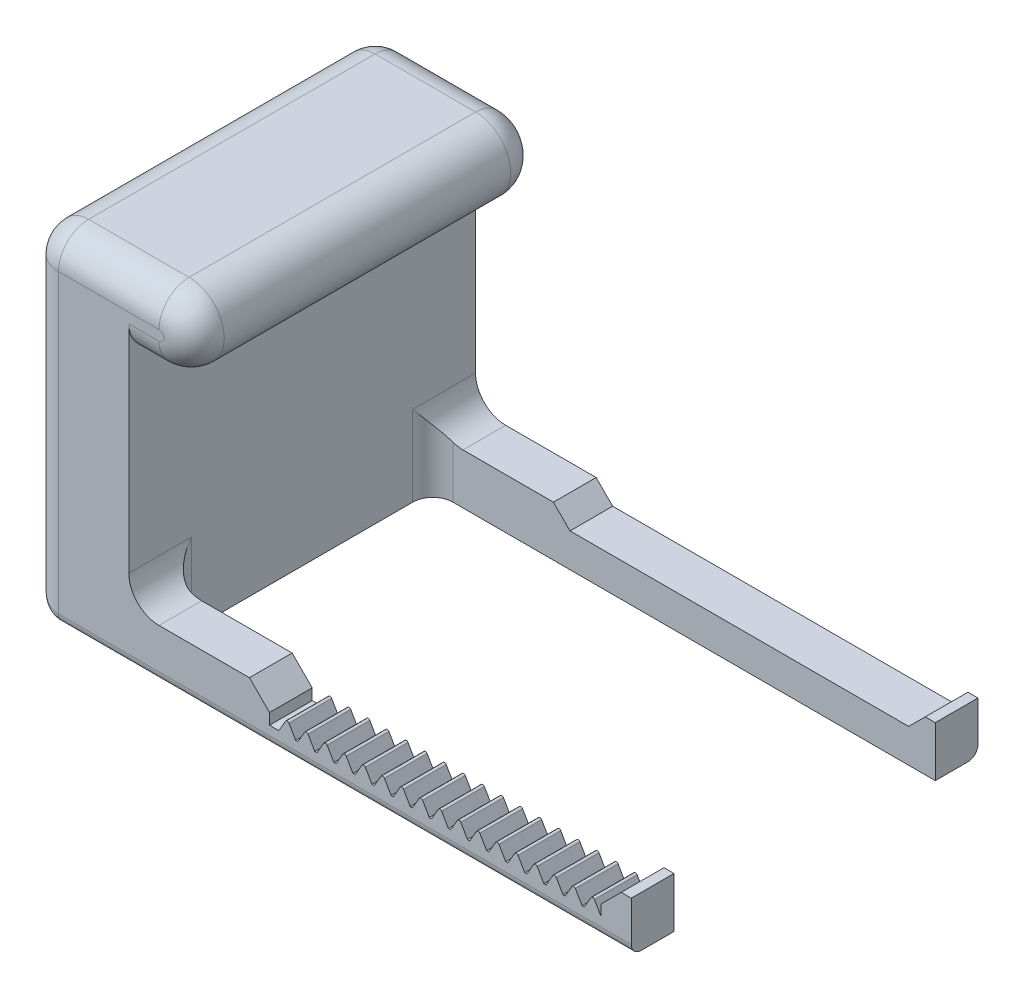
SolidWorks part; units mm, degrees
ref_plane "Front" through (0, 0, 0) normal (0, 0, 1) x (1, 0, 0)
ref_plane "Top" through (0, 0, 0) normal (0, 1, 0) x (1, 0, 0)
ref_plane "Right" through (0, 0, 0) normal (1, 0, 0) x (0, 0, -1)
sketch "Sketch1" plane through (0, 0, 0) normal (0, 1, 0) x (1, 0, 0)
  line L0 (0, 13) -> (0, -13)
  line L1 (0, 17.25) -> (-10, 17.25)
  line L2 (0, -17.25) -> (-10, -17.25)
  line L3 (-10, 17.25) -> (-10, -17.25)
  line L5 (0, 17.25) -> (50, 17.25)
  line L6 (0, 13) -> (50, 13)
  line L7 (50, 17.25) -> (50, 13)
  line L9 (0, -17.25) -> (50, -17.25)
  line L10 (0, -13) -> (50, -13)
  line L11 (50, -17.25) -> (50, -13)
  point P0 (0, 0)
  dimension "D1" = 10
  dimension "D2" = 4.25
  dimension "D3" = 26
  dimension "D4" = 50
extrude "Boss-Extrude1" add sketch "Sketch1" along normal blind 5
sketch "Sketch2" plane through (0, 5, 0) normal (0, 1, 0) x (1, 0, 0)
  line L0 (-10, -17.25) -> (50, -17.25) construction
  line L1 (-10, 17.25) -> (0, 17.25)
  line L2 (-10, 17.25) -> (-10, -17.25)
  line L3 (-10, -17.25) -> (0, -17.25)
  line L4 (0, 17.25) -> (0, -17.25)
  line L5 (0, -13) -> (0, 13) construction
extrude "Boss-Extrude2" add sketch "Sketch2" along normal blind 28.5
fillet "Fillet1" radius 3 2 edges at (0, 5, -15.125) (0, 5, 15.125)
fillet "Fillet2" radius 2 2 edges at (0, 4, 13) (0, 4, -13)
sketch "Sketch4" plane through (0, 0, 17.25) normal (0, 0, 1) x (1, 0, 0)
  line L1 (3, 26.5) -> (0, 26.5)
  line L2 (0, 33.5) -> (0, 8) construction
  line L3 (0, 26.5) -> (0, 33.5)
  line L4 (0, 33.5) -> (3, 33.5)
  arc A0 (3, 33.5) -> (3, 26.5) centre (3, 30) cw
  dimension "D1" = 7
  dimension "D2" = 3
extrude "Boss-Extrude3" add sketch "Sketch4" against normal up to surface (34.5 mm away) up to face at (11.7684, 12.0541, -17.25)
sketch "Sketch6" plane through (0, 0, 17.25) normal (0, 0, 1) x (1, 0, 0)
  line L0 (14, 1.9) -> (47, 1.9)
  line L1 (47, 5) -> (14, 5)
  line L4 (14, 5) -> (14, 1.9)
  line L6 (47, 1.9) -> (47, 5)
  line L7 (3, 5) -> (50, 5) construction
  line L8 (50, 5) -> (50, 0) construction
  dimension "D1" = 3.1
  dimension "D2" = 33
  dimension "D3" = 3
extrude "Cut-Extrude1" cut sketch "Sketch6" against normal through all
sketch "Sketch8" plane through (0, 0, 17.25) normal (0, 0, 1) x (1, 0, 0)
  line L0 (47, 1.9) -> (45.3257, 1.9)
  line L2 (45.3257, 1.9) -> (46.1628, 3.35)
  line L3 (46.1628, 3.35) -> (47, 1.9)
  dimension "D1" = 60
  dimension "D2" = 1.45
extrude "Boss-Extrude4" add sketch "Sketch8" against normal up to surface (34.5 mm away) up to face at (16.4522, 11.6291, -17.25)
pattern_linear "LPattern1" count 17 spacing 1.9 along (-1, 0, 0) of "Boss-Extrude4"
sketch "Sketch9" plane through (0, 1.9, 0) normal (0, -1, 0) x (1, 0, 0)
  line L0 (2, -13) -> (50, -13) construction
  line L1 (50, 13) -> (9.6113, 13)
  line L2 (50, 13) -> (50, -13)
  line L3 (50, -13) -> (9.6113, -13)
  line L4 (9.6113, 13) -> (9.6113, -13)
extrude "Cut-Extrude2" cut sketch "Sketch9" against normal blind 4
chamfer "Chamfer1" distance 2 angle 45 4 edges at (14, 5, 15.125) (14, 5, -15.125) (47, 5, -15.125) (47, 5, 15.125)
sketch "Sketch11" plane through (0, 0, -17.25) normal (0, 0, -1) x (-1, 0, 0)
  line L0 (-50, 0) -> (10, 0) construction
  line L1 (-49, 0) -> (-12, 0)
  line L2 (-49, 0) -> (-49, 3.35)
  line L3 (-49, 3.35) -> (-12, 3.35)
  line L4 (-12, 0) -> (-12, 3.35)
extrude "Boss-Extrude5" add sketch "Sketch11" against normal up to surface (4.25 mm away) up to face at (29.8705, 2.5341, -13)
fillet "Fillet3" radius 3 4 edges at (-10, 33.5, 0) (-10, 16.75, -17.25) (-10, 16.75, 17.25) (-10, 0, 0)
fillet "Fillet4" radius 3 8 edges at (1.5, 26.5, -17.25) (6.5, 30, -17.25) (-9.1213, 32.6213, -16.3713) (-9.1213, 32.6213, 16.3713) (1.5, 26.5, 17.25) (6.5, 30, 17.25) (-2, 33.5, -17.25) (-2, 33.5, 17.25)
fillet "Fillet5" radius 1 4 edges at (-9.1213, 0.8787, 16.3713) (21.5, 0, 17.25) (-9.1213, 0.8787, -16.3713) (21.5, 0, -17.25)
fillet "Fillet6" radius 0.2 17 edges at (46.1628, 3.35, 15.125) (44.2628, 3.35, 15.125) (42.3628, 3.35, 15.125) (40.4628, 3.35, 15.125) (38.5628, 3.35, 15.125) (36.6628, 3.35, 15.125) (34.7628, 3.35, 15.125) (32.8628, 3.35, 15.125) (30.9628, 3.35, 15.125) (29.0628, 3.35, 15.125) (27.1628, 3.35, 15.125) (25.2628, 3.35, 15.125) (23.3628, 3.35, 15.125) (21.4628, 3.35, 15.125) (19.5628, 3.35, 15.125) (17.6628, 3.35, 15.125) (15.7628, 3.35, 15.125)
